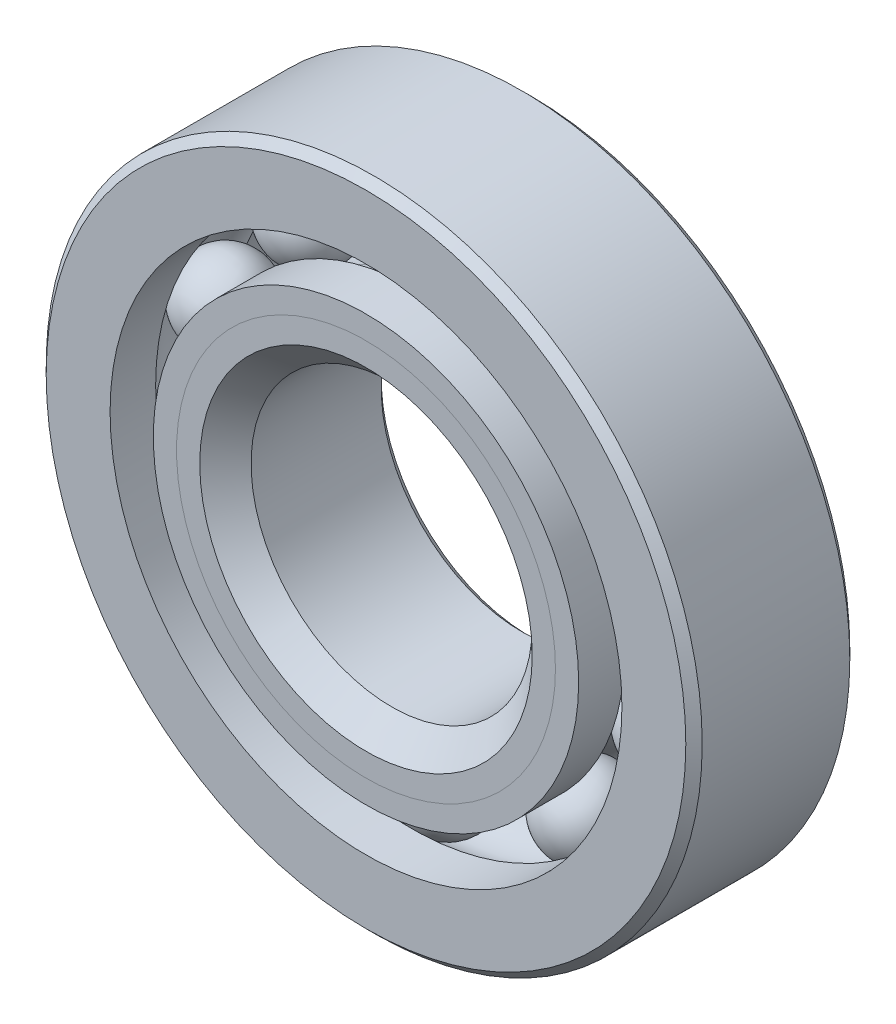
SolidWorks part; units mm, degrees
ref_plane "Front Plane" through (0, 0, 0) normal (0, 0, 1) x (1, 0, 0)
ref_plane "Top Plane" through (0, 0, 0) normal (0, 1, 0) x (1, 0, 0)
ref_plane "Right Plane" through (0, 0, 0) normal (1, 0, 0) x (0, 0, -1)
sketch "Sketch1" plane through (0, 0, 0) normal (1, 0, 0) x (0, 0, -1)
  line L0 (-2.7781, 0) -> (2.7781, 0) construction
  line L1 (0, 11.1125) -> (0, -11.1125) construction
  line L2 (2.5003, 11.1125) -> (-2.5003, 11.1125)
  line L3 (-2.5003, 11.1125) -> (-2.7781, 10.8347)
  line L4 (-2.7781, 10.8347) -> (-2.7781, 8.6702)
  line L5 (-2.7781, 8.6702) -> (-1.2347, 8.6702)
  line L6 (2.7781, 8.6702) -> (1.2347, 8.6702)
  line L7 (2.7781, 10.8347) -> (2.7781, 8.6702)
  line L8 (2.5003, 11.1125) -> (2.7781, 10.8347)
  line L9 (0, 11.1125) -> (0, 7.9375) construction
  line L10 (0, 7.9375) -> (0, 4.7625) construction
  arc A0 (-1.2347, 8.6702) -> (1.2347, 8.6702) centre (0, 7.9375) cw
  point P14 (0, 4.7625)
  dimension "Width" = 5.5562
  dimension "OD" = 22.225
  dimension "D1" = 45
  dimension "D2" = 0.2778
  dimension "D3" = 2.4694
  dimension "D4" = 0.7327
revolve "Revolve1" add sketch "Sketch1" angle 360 about L0
sketch "Sketch2" plane through (0, 0, 0) normal (1, 0, 0) x (0, 0, -1)
  line L0 (-2.7781, 7.2048) -> (-1.2347, 7.2048)
  line L1 (-2.7781, 10.8347) -> (-2.7781, -10.8347) construction
  line L2 (-2.7781, 7.2048) -> (-2.7781, 6.4185)
  line L3 (-2.7781, 6.4185) -> (-1.9918, 5.6321)
  line L4 (-1.9918, 5.6321) -> (0, 5.6321)
  line L5 (0, 11.1125) -> (0, -11.1125) construction
  line L6 (0, 5.6321) -> (0, 6.5018)
  line L7 (0, 6.5018) -> (0, 4.7625) construction
  line L8 (-2.7781, 7.2048) -> (-2.7781, 5.6321) construction
  line L9 (-2.7781, 5.6321) -> (-1.9918, 5.6321) construction
  arc A0 (-1.2347, 7.2048) -> (0, 6.5018) centre (0, 7.9375) ccw
  arc A1 (1.2347, 8.6702) -> (-1.2347, 8.6702) centre (0, 7.9375) ccw construction
  circle A2 centre (0, 7.9375) radius 1.4357 construction
  dimension "D1" = 45
revolve "Revolve2" add sketch "Sketch2" angle 360 about L0
sketch "Sketch3" plane through (0, 0, 0) normal (1, 0, 0) x (0, 0, -1)
  line L0 (-2.7781, 6.4185) -> (-1.9918, 5.6321)
  line L1 (-1.9918, 5.6321) -> (0, 5.6321)
  line L2 (0, 5.6321) -> (0, 6.5018)
  line L3 (-2.7781, 6.4185) -> (-2.7781, 5.6321)
  line L4 (-2.7781, 7.2048) -> (-2.7781, 5.6321) construction
  line L5 (-2.7781, 5.6321) -> (-1.9085, 4.7625)
  line L6 (-1.9085, 4.7625) -> (2.5003, 4.7625)
  line L7 (2.5003, 11.1125) -> (2.5003, -11.1125) construction
  line L8 (2.5003, 4.7625) -> (2.7781, 5.0403)
  line L9 (2.7781, -10.8347) -> (2.7781, 10.8347) construction
  line L10 (2.7781, 5.0403) -> (2.7781, 7.2048)
  line L11 (2.7781, 7.2048) -> (1.2347, 7.2048)
  line L13 (2.5003, 11.1125) -> (2.7781, 10.8347) construction
  circle A0 centre (0, 7.9375) radius 1.4357 construction
  arc A1 (1.2347, 7.2048) -> (0, 6.5018) centre (0, 7.9375) cw
revolve "Revolve3" add sketch "Sketch3" angle 360 about L0
sketch "Sketch4" plane through (0, 0, 0) normal (1, 0, 0) x (0, 0, -1)
  line L0 (-1.4357, 7.9375) -> (1.4357, 7.9375)
  circle A1 centre (0, 7.9375) radius 1.4357 construction
  arc A2 (-1.4357, 7.9375) -> (1.4357, 7.9375) centre (0, 7.9375) cw
  arc A3 (1.2347, 8.6702) -> (-1.2347, 8.6702) centre (0, 7.9375) ccw construction
revolve "Revolve4" add sketch "Sketch4" angle 360 about L0
ref_axis "Axis1" through (0, 0, -2.7781) along (0, 0, 1)
pattern_circular "CirPattern1" count 10 every 36 about axis through (0, 0, -2.7781) along (0, 0, 1) of bodies 104
equation "\"D2@Sketch1\" = \"Width@Sketch1\"*.05"
equation "\"D3@Sketch1\" = \"Width@Sketch1\"/2.25"
equation "\"D4@Sketch1\" = (((\"OD@Sketch1\"-\"Width@Sketch1\")/2)/3.25)/3.5"
equation "\"D2@CirPattern1\" = 360/\"Balls@CirPattern1\""
